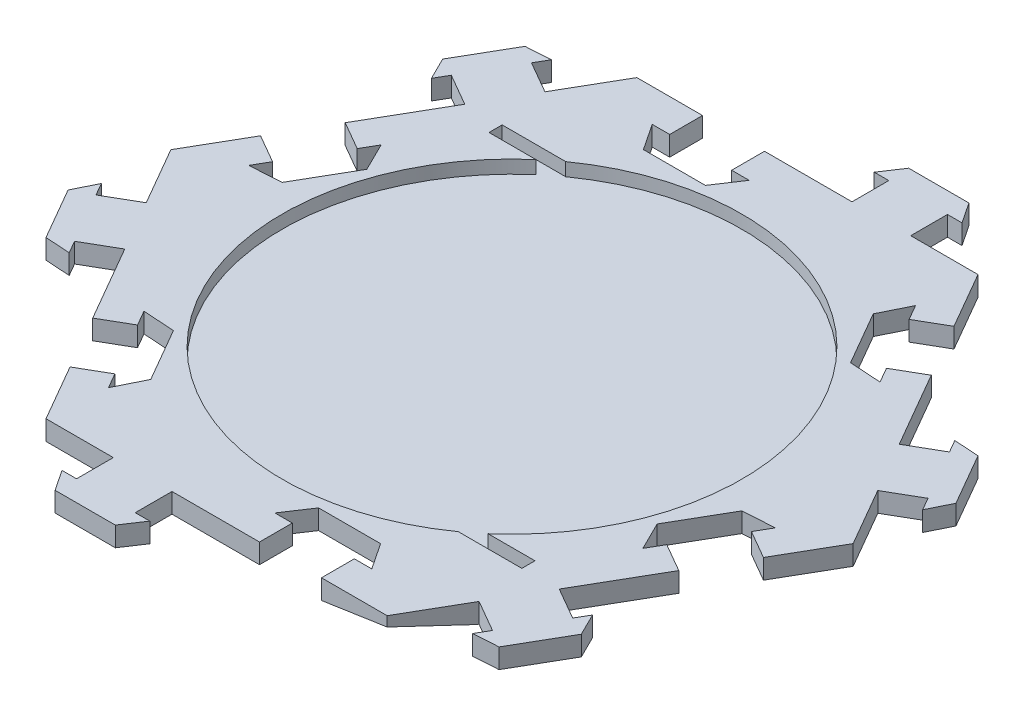
SolidWorks part; units mm, degrees
ref_plane "Front Plane" through (0, 0, 0) normal (0, 0, 1) x (1, 0, 0)
ref_plane "Top Plane" through (0, 0, 0) normal (0, 1, 0) x (1, 0, 0)
ref_plane "Right Plane" through (0, 0, 0) normal (1, 0, 0) x (0, 0, -1)
sketch "Sketch1" plane through (0, 0, 0) normal (0, 1, 0) x (1, 0, 0)
  line L0 (-15.9808, 45) -> (-15.9808, 40)
  line L1 (25.9808, -45) -> (51.9615, 0)
  line L2 (51.9615, 0) -> (25.9808, 45)
  line L3 (25.9808, 45) -> (-25.9808, 45)
  line L4 (-25.9808, 45) -> (-51.9615, 0)
  line L5 (-51.9615, 0) -> (-25.9808, -45)
  line L6 (-25.9808, -45) -> (25.9808, -45)
  line L7 (-15.9808, 40) -> (-18.6446, 40)
  line L8 (-18.6446, 40) -> (-15.9808, 36)
  line L9 (-15.9808, 36) -> (-6.5403, 36)
  line L10 (-6.5403, 36) -> (-3.8765, 40)
  line L11 (-3.8765, 40) -> (-6.5403, 40)
  line L12 (-6.5403, 40) -> (-6.5403, 45)
  line L13 (-15.9808, 40) -> (-15.9808, 36) construction
  line L14 (6.5403, 45) -> (6.5403, 50) construction
  line L15 (6.5403, 50) -> (3.8765, 50) construction
  line L16 (3.8765, 50) -> (6.5403, 54) construction
  line L17 (6.5403, 54) -> (15.9808, 54) construction
  line L18 (15.9808, 54) -> (18.6446, 50) construction
  line L19 (18.6446, 50) -> (15.9808, 50) construction
  line L20 (15.9808, 50) -> (15.9808, 45) construction
  line L21 (6.5403, 50) -> (6.5403, 54) construction
  line L22 (6.7903, 50.25) -> (6.7903, 45)
  line L23 (6.7903, 50.25) -> (4.3433, 50.25) construction
  line L24 (4.3433, 50.25) -> (6.6742, 53.75) construction
  line L25 (6.6742, 53.75) -> (15.8469, 53.75) construction
  line L26 (15.8469, 53.75) -> (18.1777, 50.25) construction
  line L27 (18.1777, 50.25) -> (15.7308, 50.25) construction
  line L28 (15.7308, 50.25) -> (15.7308, 45)
  line L29 (15.7308, 50.25) -> (15.7308, 50.6)
  line L30 (7.0097, 50.6) -> (4.5764, 50.6)
  line L31 (4.5764, 50.6) -> (6.6742, 53.75)
  line L32 (6.6742, 53.75) -> (15.8469, 53.75)
  line L33 (15.8469, 53.75) -> (17.9446, 50.6)
  line L34 (17.9446, 50.6) -> (15.5089, 50.6)
  line L35 (6.7903, 50.25) -> (6.7903, 50.6)
  line L36 (30.9808, 36.3397) -> (26.6506, 33.8397)
  line L37 (26.6506, 33.8397) -> (25.3187, 36.1467)
  line L38 (25.3187, 36.1467) -> (23.1865, 31.8397)
  line L39 (23.1865, 31.8397) -> (27.9068, 23.664)
  line L40 (27.9068, 23.664) -> (32.7028, 23.3571)
  line L41 (32.7028, 23.3571) -> (31.3709, 25.664)
  line L42 (31.3709, 25.664) -> (35.701, 28.164)
  line L43 (51.3832, 11.5018) -> (46.8365, 8.8768)
  line L44 (46.9129, 19.2444) -> (42.3663, 16.6194)
  line L45 (46.9129, 19.2444) -> (47.216, 19.4194)
  line L46 (51.3832, 11.5018) -> (51.6863, 11.6768)
  line L47 (52.7932, 9.7595) -> (51.5754, 11.8689)
  line L48 (54.4723, 13.1512) -> (52.7932, 9.7595)
  line L49 (49.8859, 21.095) -> (54.4723, 13.1512)
  line L50 (46.1091, 21.3367) -> (49.8859, 21.095)
  line L51 (47.3257, 19.2294) -> (46.1091, 21.3367)
  line L52 (46.9615, -8.6603) -> (42.6314, -6.1603)
  line L53 (42.6314, -6.1603) -> (43.9633, -3.8533)
  line L54 (43.9633, -3.8533) -> (39.1673, -4.1603)
  line L55 (39.1673, -4.1603) -> (34.4471, -12.336)
  line L56 (34.4471, -12.336) -> (36.5793, -16.6429)
  line L57 (36.5793, -16.6429) -> (37.9112, -14.336)
  line L58 (37.9112, -14.336) -> (42.2413, -16.836)
  line L59 (35.6524, -38.7482) -> (31.1058, -36.1232)
  line L60 (40.1226, -31.0056) -> (35.576, -28.3806)
  line L61 (40.1226, -31.0056) -> (40.4257, -31.1806)
  line L62 (35.6524, -38.7482) -> (35.9555, -38.9232)
  line L63 (34.8486, -40.8405) -> (36.0664, -38.7311)
  line L64 (38.6254, -40.5988) -> (34.8486, -40.8405)
  line L65 (43.2118, -32.655) -> (38.6254, -40.5988)
  line L66 (41.5327, -29.2633) -> (43.2118, -32.655)
  line L67 (40.316, -31.3706) -> (41.5327, -29.2633)
  line L68 (15.9808, -45) -> (15.9808, -40)
  line L69 (15.9808, -40) -> (18.6446, -40)
  line L70 (18.6446, -40) -> (15.9808, -36)
  line L71 (15.9808, -36) -> (6.5403, -36)
  line L72 (6.5403, -36) -> (3.8765, -40)
  line L73 (3.8765, -40) -> (6.5403, -40)
  line L74 (6.5403, -40) -> (6.5403, -45)
  line L75 (-15.7308, -50.25) -> (-15.7308, -45)
  line L76 (-6.7903, -50.25) -> (-6.7903, -45)
  line L77 (-6.7903, -50.25) -> (-6.7903, -50.6)
  line L78 (-15.7308, -50.25) -> (-15.7308, -50.6)
  line L79 (-17.9446, -50.6) -> (-15.5089, -50.6)
  line L80 (-15.8469, -53.75) -> (-17.9446, -50.6)
  line L81 (-6.6742, -53.75) -> (-15.8469, -53.75)
  line L82 (-4.5764, -50.6) -> (-6.6742, -53.75)
  line L83 (-7.0097, -50.6) -> (-4.5764, -50.6)
  line L84 (-30.9808, -36.3397) -> (-26.6506, -33.8397)
  line L85 (-26.6506, -33.8397) -> (-25.3187, -36.1467)
  line L86 (-25.3187, -36.1467) -> (-23.1865, -31.8397)
  line L87 (-23.1865, -31.8397) -> (-27.9068, -23.664)
  line L88 (-27.9068, -23.664) -> (-32.7028, -23.3571)
  line L89 (-32.7028, -23.3571) -> (-31.3709, -25.664)
  line L90 (-31.3709, -25.664) -> (-35.701, -28.164)
  line L91 (-51.3832, -11.5018) -> (-46.8365, -8.8768)
  line L92 (-46.9129, -19.2444) -> (-42.3663, -16.6194)
  line L93 (-46.9129, -19.2444) -> (-47.216, -19.4194)
  line L94 (-51.3832, -11.5018) -> (-51.6863, -11.6768)
  line L95 (-52.7932, -9.7595) -> (-51.5754, -11.8689)
  line L96 (-54.4723, -13.1512) -> (-52.7932, -9.7595)
  line L97 (-49.8859, -21.095) -> (-54.4723, -13.1512)
  line L98 (-46.1091, -21.3367) -> (-49.8859, -21.095)
  line L99 (-47.3257, -19.2294) -> (-46.1091, -21.3367)
  line L100 (-46.9615, 8.6603) -> (-42.6314, 6.1603)
  line L101 (-42.6314, 6.1603) -> (-43.9633, 3.8533)
  line L102 (-43.9633, 3.8533) -> (-39.1673, 4.1603)
  line L103 (-39.1673, 4.1603) -> (-34.4471, 12.336)
  line L104 (-34.4471, 12.336) -> (-36.5793, 16.6429)
  line L105 (-36.5793, 16.6429) -> (-37.9112, 14.336)
  line L106 (-37.9112, 14.336) -> (-42.2413, 16.836)
  line L107 (-35.6524, 38.7482) -> (-31.1058, 36.1232)
  line L108 (-40.1226, 31.0056) -> (-35.576, 28.3806)
  line L109 (-40.1226, 31.0056) -> (-40.4257, 31.1806)
  line L110 (-35.6524, 38.7482) -> (-35.9555, 38.9232)
  line L111 (-34.8486, 40.8405) -> (-36.0664, 38.7311)
  line L112 (-38.6254, 40.5988) -> (-34.8486, 40.8405)
  line L113 (-43.2118, 32.655) -> (-38.6254, 40.5988)
  line L114 (-41.5327, 29.2633) -> (-43.2118, 32.655)
  line L115 (-40.316, 31.3706) -> (-41.5327, 29.2633)
  line L116 (6.7903, 45) -> (6.7903, 50.25) construction
  line L117 (15.7308, 50.25) -> (15.7308, 45) construction
  line L118 (0, 5) -> (0, -2) construction
  line L119 (2.5, -2) -> (0, 5)
  line L120 (0, 5) -> (-2.5, -2)
  line L121 (-2.5, -2) -> (2.5, -2)
  circle A0 centre (0, 0) radius 45 construction
  circle A1 centre (0, 0) radius 45 construction
  circle A2 centre (0, 0) radius 35
  point P145 (0, 0)
  point P146 (-0.0013, -0.0009)
  dimension "D1" = 90
  dimension "D4" = 10
  dimension "D2" = 5
  dimension "D3" = 4
  dimension "D5" = 10
  dimension "D6" = 0.25
  dimension "D7" = 0.35
  dimension "D8" = 6
  dimension "D10" = 0.6
  dimension "D9" = 0.25
  dimension "D12" = 5
  dimension "D13" = 7
  dimension "D14" = 2
  dimension "D11" = 10
extrude "Boss-Extrude1" add sketch "Sketch1" along normal blind 3 contours L2 L3 L4 | L3 | L2 | L4 | L1 | L5 | L6 region at (-17.3555, 0, -42.5) region at (11.2605, 0, -49.5746) region at (-37.3026, 0, -34.5392) region at (48.5631, 0, -15.0354) region at (-48.5631, 0, 15.0354) region at (37.3026, 0, 34.5392) region at (-11.2605, 0, 49.5746)
extrude "Boss-Extrude2" add sketch "Sketch1<3>" along normal blind 1 contours A2 | L120 L121 L119 region at (0, 0, -0.3333) region at (-34.0101, 0, 0)
sketch "Sketch1<3>" plane through (0, 0, 0) normal (0, 1, 0) x (1, 0, 0) same geometry as "Sketch1"
sketch "Sketch2" plane through (0, 1, 0) normal (0, 1, 0) x (1, 0, 0)
  line L0 (0, 27.5) -> (0, -27.5) construction
  line L1 (0, 27.5) -> (-30, 27.5)
  line L2 (0, -27.5) -> (30, -27.5)
  dimension "D1" = 55
  dimension "D2" = 30
extrude "Cut-Extrude-Thin1" cut sketch "Sketch2" along normal blind 10 thin contours L2 | L1 thin type mid plane wall 2
ref_plane "Plane1" through (0, 0, 0) normal (0.866, 0, -0.5) x (-0.5, 0, -0.866)
sketch "Sketch4" plane through (0, 0, 0) normal (0.866, 0, -0.5) x (-0.5, 0, -0.866)
  line L0 (-51.9615, 1.5) -> (-46.9615, 0)
  line L1 (-46.9615, 0) -> (-51.9615, 0)
  line L2 (-51.9615, 0) -> (-51.9615, 1.5)
  line L3 (-51.9615, 3) -> (-51.9615, 0) construction
extrude "Cut-Extrude1" cut sketch "Sketch4" against normal blind 10 and the other way blind 8.7
